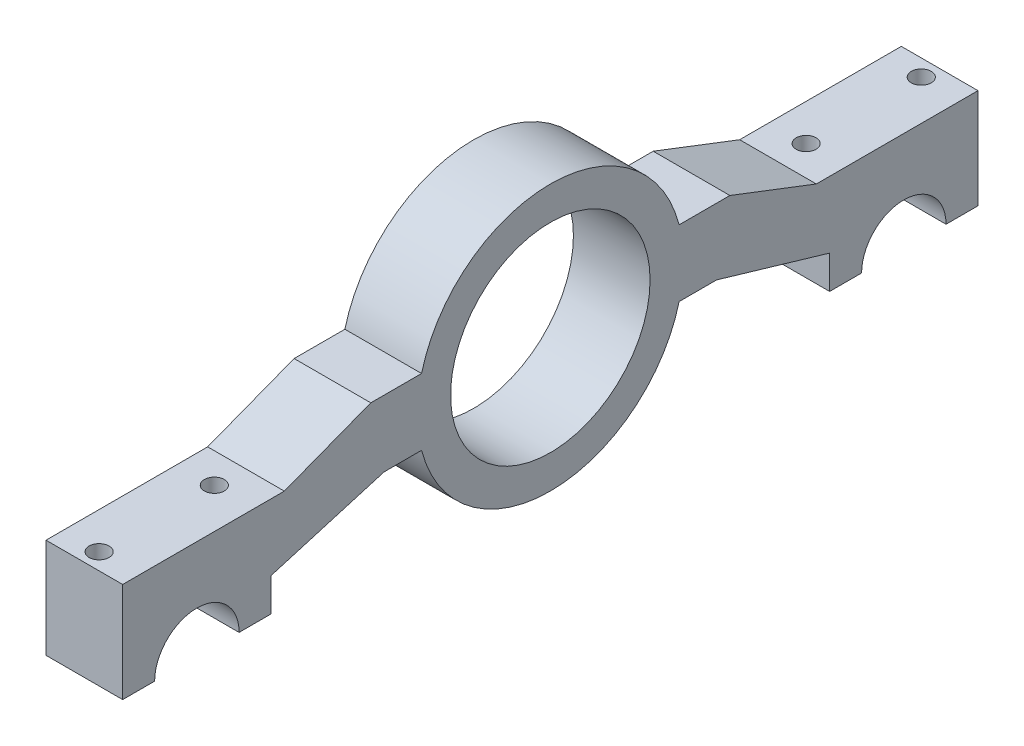
SolidWorks part; units mm, degrees
ref_plane "Front Plane" through (0, 0, 0) normal (0, 0, 1) x (1, 0, 0)
ref_plane "Top Plane" through (0, 0, 0) normal (0, 1, 0) x (1, 0, 0)
ref_plane "Right Plane" through (0, 0, 0) normal (1, 0, 0) x (0, 0, -1)
sketch "Sketch1" plane through (0, 0, 0) normal (0, 0, 1) x (1, 0, 0)
  circle A0 centre (0, 0) radius 4.765
  circle A1 centre (0, 0) radius 5.765
  dimension "D1" = 9.53
  dimension "D2" = 11.53
extrude "Boss-Extrude1" add sketch "Sketch1" along normal blind 10
sketch "Sketch2" plane through (0, 0, 0) normal (0, 1, 0) x (1, 0, 0)
  line L1 (5.765, -10) -> (-5.765, -10)
  line L2 (5.765, -10) -> (5.765, 0)
  line L3 (5.765, 0) -> (-5.765, 0)
  line L4 (-5.765, -10) -> (-5.765, 0)
extrude "Boss-Extrude2" add sketch "Sketch2" along normal blind 10
sketch "Sketch3" plane through (0, 0, 0) normal (0, 0, -1) x (-1, 0, 0)
  line L0 (-4.765, 0) -> (4.765, 0) construction
  circle A0 centre (0, 0) radius 4.765
extrude "Cut-Extrude1" cut sketch "Sketch3" against normal blind 10
sketch "Sketch8" plane through (0, 10, 0) normal (0, 1, 0) x (1, 0, 0)
  line L1 (-5.765, -10) -> (5.765, -10)
  line L2 (-5.765, -10) -> (-5.765, 0)
  line L3 (-5.765, 0) -> (5.765, 0)
  line L4 (5.765, -10) -> (5.765, 0)
  line L5 (2.765, -10) -> (-2.765, -10)
  line L7 (2.765, 0) -> (-2.765, 0)
  point P6 (0, -5)
  line M5 (5.765, -10) -> (5.765, 0)
  line M6 (5.765, 0) -> (-5.765, 0)
  line M7 (-5.765, 0) -> (-5.765, -10)
  line M8 (-5.765, -10) -> (5.765, -10)
extrude "Boss-Extrude5" add sketch "Sketch8" along normal blind 10 contours M8 M5 M6 | M8 M6 M7 region at (0, 10, 5)
sketch "Sketch9" plane through (5.765, 0, 0) normal (1, 0, 0) x (0, 0, -1)
  line L0 (0, 20) -> (0, 0) construction
  line L1 (-10, 20) -> (0, 20) construction
  circle A0 centre (-5, 15) radius 3.5
  dimension "D3" = 7
  dimension "D1" = 5
  dimension "D2" = 5
extrude "Cut-Extrude4" cut sketch "Sketch9" against normal through all
sketch "Sketch11" plane through (0, 0, 0) normal (0, 0, -1) x (-1, 0, 0)
  line L0 (5.765, 20) -> (5.765, 0) construction
  line L1 (5.765, 10) -> (-5.765, 10)
  line L2 (5.765, 10) -> (5.765, 20)
  line L3 (5.765, 20) -> (-5.765, 20)
  line L4 (-5.765, 10) -> (-5.765, 20)
  line L5 (-5.765, 20) -> (-5.765, 0) construction
  line L6 (-5.765, 20) -> (5.765, 20) construction
  dimension "D1" = 10
extrude "Boss-Extrude6" add sketch "Sketch11" along normal blind 48.155
sketch "Sketch12" plane through (0, 0, 0) normal (1, 0, 0) x (0, 0, -1)
  line L1 (48.155, 10) -> (48.155, 0) construction
  line L2 (59.31, 0) -> (59.31, 20)
  line L4 (47, 20) -> (59.31, 20)
  line L5 (-10, 20) -> (48.155, 20) construction
  line L6 (37, 0) -> (37, 20)
  line L7 (37, 20) -> (47, 20)
  arc A1 (37, 0) -> (59.31, 0) centre (48.155, 0) ccw
  circle A2 centre (48.155, 0) radius 6.35
  dimension "D2" = 12.7
  dimension "D1" = 10
  dimension "D3" = 10
extrude "Boss-Extrude7" add sketch "Sketch12" along normal mid plane 11.53
sketch "Sketch13" plane through (-5.765, 0, 0) normal (-1, 0, 0) x (0, 0, 1)
  line L0 (10, 20) -> (10, 0) construction
  line L1 (0, 10) -> (10, 10)
  line L2 (0, 10) -> (0, -10)
  line L3 (0, -10) -> (10, -10)
  line L4 (10, 10) -> (10, -10)
  dimension "D1" = 20
extrude "Cut-Extrude5" cut sketch "Sketch13" against normal blind 11.53
sketch "Sketch14" plane through (-5.765, 0, 0) normal (-1, 0, 0) x (0, 0, 1)
  line L0 (-37, 10) -> (10, 10) construction
  line L2 (5, 18.5) -> (5, 10)
  line L3 (5, 10) -> (10, 10)
  line L4 (10, 18.5) -> (10, 10)
  line L5 (5, 18.5) -> (5, 20)
  line L6 (-59.31, 20) -> (10, 20) construction
  line L7 (5, 20) -> (10, 20)
  line L8 (10, 20) -> (10, 18.5)
  circle A0 centre (5, 15) radius 3.5 construction
extrude "Cut-Extrude6" cut sketch "Sketch14" against normal blind 11.53
mirror "Mirror1" about plane through (5.765, 18.5, 5) normal (0, 0, -1) of "Boss-Extrude6", "Boss-Extrude2", "Boss-Extrude5", "Cut-Extrude4", "Boss-Extrude7", "Cut-Extrude6"
sketch "Sketch15" plane through (-5.765, 0, 0) normal (-1, 0, 0) x (0, 0, 1)
  line L1 (10, 0) -> (0, 0)
  line L2 (10, 0) -> (10, 10)
  line L3 (10, 10) -> (0, 10)
  line L4 (0, 0) -> (0, 10)
extrude "Cut-Extrude7" cut sketch "Sketch15" against normal blind 11.53
sketch "Sketch17" plane through (-5.765, 0, 0) normal (-1, 0, 0) x (0, 0, 1)
  line L0 (5, 20) -> (69.31, 20) construction
  line L1 (-4.335, 20) -> (6.8697, 20)
  line L2 (-4.335, 20) -> (-4.335, 10)
  line L3 (-4.335, 10) -> (6.8697, 10)
  line L4 (6.8697, 20) -> (6.8697, 10)
  line L5 (47, 10) -> (5, 10) construction
extrude "Boss-Extrude10" add sketch "Sketch17" against normal blind 11.53
sketch "Sketch19" plane through (-5.765, 0, 0) normal (-1, 0, 0) x (0, 0, 1)
  line L0 (-41.805, 0) -> (69.31, 0)
  line L1 (69.31, 0) -> (69.31, -15)
  line L2 (69.31, -15) -> (-59.31, -15)
  line L3 (-59.31, -15) -> (-59.31, 0)
  line L4 (-59.31, 0) -> (-41.805, 0)
  circle A0 centre (-48.155, 0) radius 6.35 construction
  dimension "D1" = 15
  dimension "D2" = 0
extrude "Cut-Extrude9" cut sketch "Sketch19" against normal through all
sketch "Sketch20" plane through (0, 0, 0) normal (0, -1, 0) x (-1, 0, 0)
  line L0 (-5.765, 59.31) -> (5.765, 59.31) construction
  line L1 (5.765, 54.505) -> (5.765, 59.31) construction
  line L2 (5.765, 37) -> (5.765, 41.805) construction
  line L3 (-5.765, 37) -> (5.765, 37) construction
  line L4 (-5.765, -47) -> (5.765, -47) construction
  line L5 (-5.765, -69.31) -> (5.765, -69.31) construction
  line L6 (5.765, -69.31) -> (5.765, -64.505) construction
  line L7 (5.765, -51.805) -> (5.765, -47) construction
  circle A0 centre (0.265, 56.81) radius 1.5
  circle A2 centre (0.265, 39.5) radius 1.5
  circle A4 centre (0.265, -66.8241) radius 1.5
  circle A5 centre (0.265, -49.5) radius 1.5
  point P20 (0, -69.31)
  dimension "D1" = 3
  dimension "D5" = 2.5
  dimension "D6" = 3
  dimension "D7" = 3
  dimension "D8" = 3
  dimension "D9" = 2.5
  dimension "D10" = 2.5
  dimension "D2" = 2.5
  dimension "D3" = 5.5
  dimension "D4" = 5.5
  dimension "D11" = 5.5
  dimension "D12" = 5.5
extrude "Cut-Extrude10" cut sketch "Sketch20" against normal through all
sketch "Sketch22" plane through (5.765, 0, 0) normal (1, 0, 0) x (0, 0, -1)
  line L0 (-47, 10) -> (-47, 0) construction
  line L1 (-69.31, 20) -> (-45, 20)
  line L2 (-69.31, 20) -> (-69.31, 15)
  line L3 (-69.31, 15) -> (-45, 15)
  line L4 (-45, 20) -> (-45, 15)
  line L5 (59.31, 20) -> (35, 20)
  line L6 (59.31, 20) -> (59.31, 15)
  line L7 (59.31, 15) -> (35, 15)
  line L8 (35, 20) -> (35, 15)
  line L9 (37, 10) -> (37, 0) construction
  line L10 (-45, 15) -> (-32, 20)
  line L11 (-69.31, 20) -> (59.31, 20) construction
  line L12 (-32, 20) -> (22, 20)
  line L13 (22, 20) -> (35, 15)
  line M4 (-69.31, 20) -> (-69.31, 0)
  line M14 (59.31, 0) -> (59.31, 20)
  line M15 (59.31, 20) -> (-69.31, 20)
  dimension "D1" = 2
  dimension "D2" = 2
  dimension "D3" = 5
  dimension "D4" = 5
  dimension "D5" = 13
  dimension "D6" = 13
extrude "Cut-Extrude11" cut sketch "Sketch22" against normal through all contours L4 L10 M15 | L4 L3 M15 M4 | L13 L8 M15 | L8 L7 M15 M14 region at (5.765, 18.3333, -30.6667) region at (5.765, 17.5, 57.155) region at (5.765, 18.3333, 40.6667) region at (5.765, 17.5, -47.155)
sketch "Sketch23" plane through (5.765, 0, 0) normal (1, 0, 0) x (0, 0, -1)
  line L0 (-47, 5) -> (-30, 10)
  line L1 (-47, 10) -> (-47, 0) construction
  line L2 (37, 10) -> (-47, 10) construction
  line L3 (-30, 10) -> (20, 10)
  line L4 (20, 10) -> (37, 5)
  line L5 (37, 10) -> (37, 0) construction
  line L14 (-47, 10) -> (37, 10)
  line L15 (-47, 10) -> (37, 10)
  line L18 (-69.31, 15) -> (-69.31, 0)
  line L19 (-69.31, 0) -> (-64.505, 0)
  line L20 (22, 20) -> (-32, 20)
  line L21 (-32, 20) -> (-45, 15)
  line L22 (-45, 15) -> (-69.31, 15)
  line L27 (-51.805, 0) -> (-47, 0)
  line L28 (-47, 0) -> (-47, 10)
  line L29 (-47, 0) -> (-47, 10)
  line L30 (37, 10) -> (37, 0)
  line L31 (37, 10) -> (37, 0)
  line L32 (59.31, 15) -> (35, 15)
  line L33 (35, 15) -> (22, 20)
  line L48 (37, 0) -> (41.805, 0)
  line L49 (54.505, 0) -> (59.31, 0)
  line L50 (59.31, 0) -> (59.31, 15)
  arc A2 (-51.805, 0) -> (-64.505, 0) centre (-58.155, 0) ccw
  arc A3 (54.505, 0) -> (41.805, 0) centre (48.155, 0) ccw
  line M25 (-47, 0) -> (-47, 10)
  line M26 (-47, 10) -> (37, 10)
  line M27 (37, 10) -> (37, 0)
  dimension "D1" = 5
  dimension "D2" = 17
  dimension "D3" = 17
  dimension "D4" = 5
  dimension "D5" = 0
extrude "Boss-Extrude11" add sketch "Sketch23" against normal blind 11.53 contours L0 M25 M26 | L4 M26 M27 region at (5.765, 8.3333, 41.3333) region at (5.765, 8.3333, -31.3333)
sketch "Sketch25" plane through (5.765, 0, 0) normal (1, 0, 0) x (0, 0, -1)
  circle A0 centre (-5, 15) radius 15
  circle A1 centre (-5, 15) radius 20
  dimension "D1" = 30
  dimension "D2" = 40
extrude "Boss-Extrude12" add sketch "Sketch25" against normal blind 11.53
sketch "Sketch26" plane through (5.765, 0, 0) normal (1, 0, 0) x (0, 0, -1)
  circle A0 centre (-5, 15) radius 15
extrude "Cut-Extrude12" cut sketch "Sketch26" against normal through all
